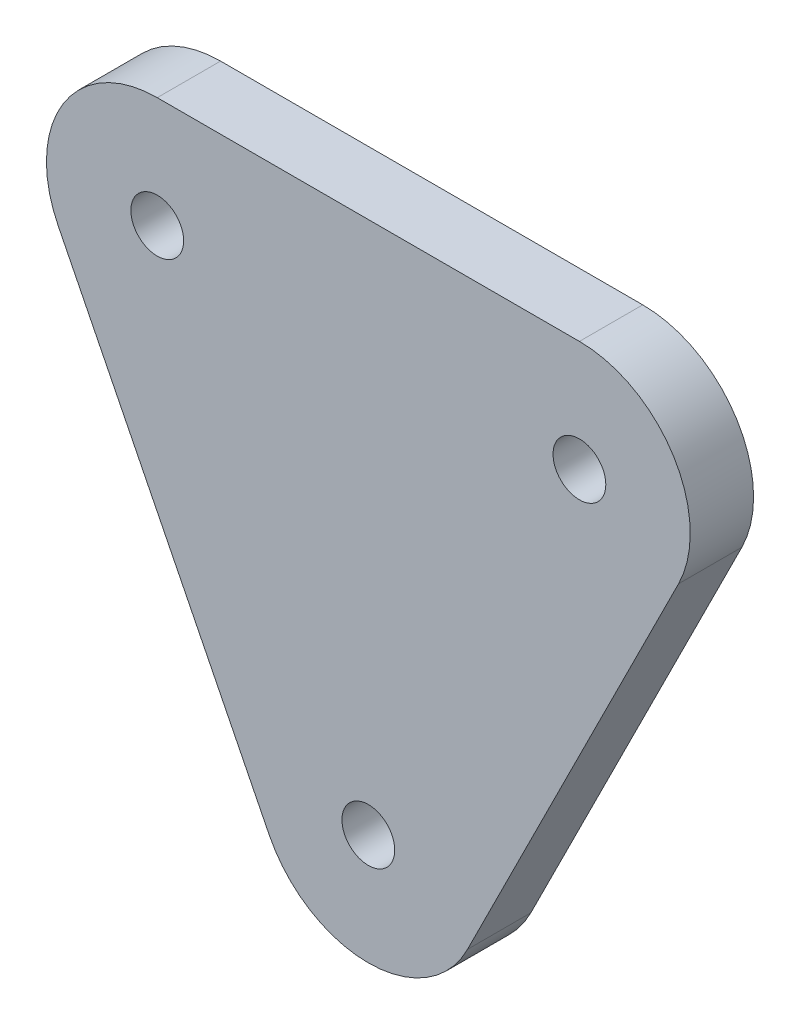
SolidWorks part; units mm, degrees
ref_plane "Plano frontal" through (0, 0, 0) normal (0, 0, 1) x (1, 0, 0)
ref_plane "Plano superior" through (0, 0, 0) normal (0, 1, 0) x (1, 0, 0)
ref_plane "Plano direito" through (0, 0, 0) normal (1, 0, 0) x (0, 0, -1)
sketch "Esboço1" plane through (0, 0, 0) normal (0, 0, 1) x (1, 0, 0)
  line L0 (-20, 30.5) -> (20, 30.5)
  line L1 (-20, 20) -> (20, 20) construction
  line L2 (-20, 20) -> (-20, -20) construction
  line L3 (-20, -20) -> (20, -20) construction
  line L4 (20, 20) -> (20, -20) construction
  line L5 (-20, 20) -> (20, -20) construction
  line L6 (-20, -20) -> (20, 20) construction
  line L7 (29.3915, 15.3043) -> (9.3915, -24.6957)
  line L8 (-29.3915, 15.3043) -> (-9.3915, -24.6957)
  circle A0 centre (-20, 20) radius 2.5
  circle A1 centre (20, 20) radius 2.5
  circle A2 centre (0, -20) radius 2.5
  arc A3 (-20, 30.5) -> (-29.3915, 15.3043) centre (-20, 20) ccw
  arc A4 (29.3915, 15.3043) -> (20, 30.5) centre (20, 20) ccw
  arc A5 (-9.3915, -24.6957) -> (9.3915, -24.6957) centre (0, -20) ccw
  circle A7 centre (0, -20) radius 10.5 construction
  circle A8 centre (20, 20) radius 10.5 construction
  circle A9 centre (-20, 20) radius 10.5 construction
  point P0 (0, 0)
  point P13 (-8, 22)
  point P15 (32, 22)
  point P18 (12, -22)
  dimension "D3" = 5
  dimension "D1" = 40
  dimension "D2" = 40
  dimension "D4" = 8
extrude "Ressalto-extrusão1" add sketch "Esboço1" along normal blind 6
